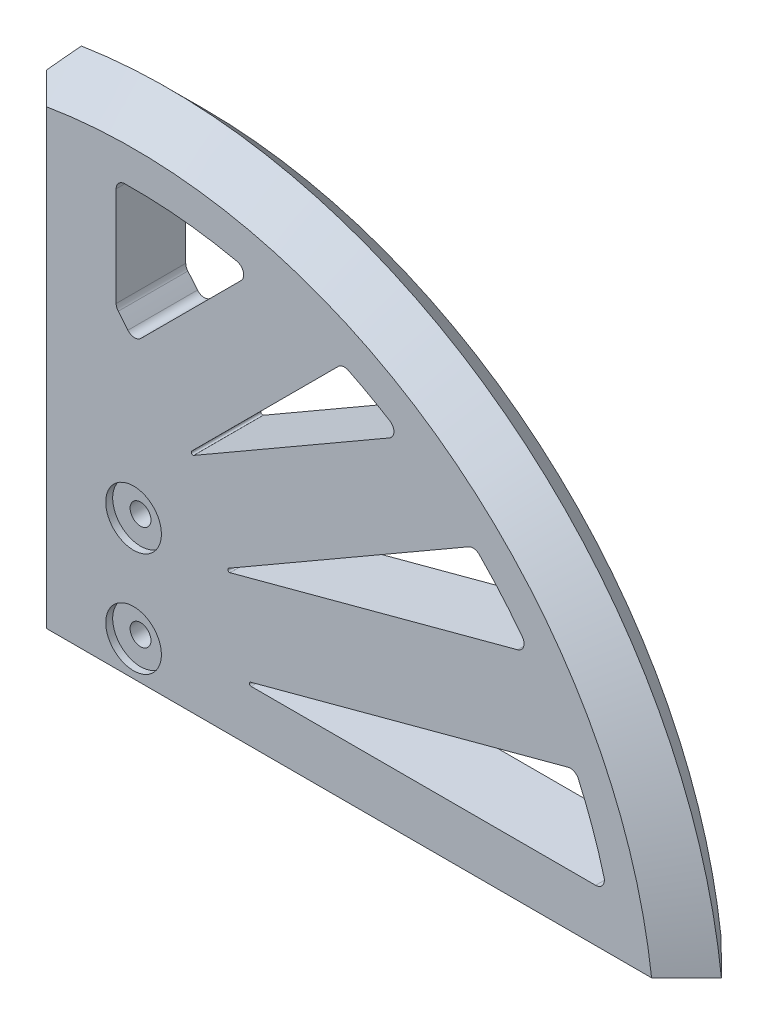
SolidWorks part; units mm, degrees
ref_plane "Front Plane" through (0, 0, 0) normal (0, 0, 1) x (1, 0, 0)
ref_plane "Top Plane" through (0, 0, 0) normal (0, 1, 0) x (1, 0, 0)
ref_plane "Right Plane" through (0, 0, 0) normal (1, 0, 0) x (0, 0, -1)
sketch "Sketch1" plane through (0, 0, 0) normal (0, 0, 1) x (1, 0, 0)
  line L0 (0, 0) -> (0, 27.8325)
  line L1 (0, 0) -> (37.7969, 0)
  line L3 (12, 3) -> (33.211, 3)
  line L6 (5, 18) -> (5, 24.3821)
  line L7 (12, 3) -> (31.3937, 8.1965)
  line L9 (10.8085, 7.8571) -> (28.7851, 12.6739)
  line L12 (10.8085, 7.8571) -> (25.5994, 16.3966)
  line L14 (8.8112, 12.4775) -> (21.4315, 19.7638)
  line L16 (8.8112, 12.4775) -> (18.0217, 21.6879)
  line L17 (12.8195, 23.5568) -> (6.0223, 16.7597)
  circle A2 centre (6, 2) radius 0.6
  circle A3 centre (6, 8) radius 0.6
  arc A17 (0, 27.8325) -> (37.7969, 0) centre (6, -3.6) cw
  arc A24 (5, 24.3821) -> (33.211, 3) centre (6, -3.6) cw
  arc A25 (5, 18) -> (12, 3) centre (-17.6305, -1.6942) cw
  point P36 (0, 0)
  dimension "D4" = 1.2
  dimension "D12" = 6
  dimension "D14" = 32
  dimension "D15" = 5
  dimension "D13" = 12
  dimension "D9" = 3
  dimension "D18" = 30
  dimension "D7" = 28
  dimension "D8" = 30
  dimension "D3" = 2
  dimension "D6" = 6
  dimension "D10" = 3.6
  dimension "D11" = 5
  dimension "D16" = 15
  dimension "D17" = 5
  dimension "D19" = 5
  dimension "D20" = 45
  dimension "20" = 18
  dimension "D5" = 2
extrude "Boss-Extrude1" add sketch "Sketch1" along normal blind 4 contours A17 L0 L1 A25 L6 A24 L3 A3 A2 | L9 A25 L7 A24 | L14 A25 L12 A24 | L6 A25 L16 A24 L17 region at (0.4728, 13.9162, 0) region at (20.8325, 7.9222, 0) region at (16.7737, 14.1119, 0) region at (11.5805, 18.6055, 0)
fillet "Fillet3" radius 0.1 3 edges at (8.8112, 12.4775, 2) (10.8085, 7.8571, 2) (12, 3, 2)
fillet "Fillet4" radius 0.5 10 edges at (33.211, 3, 2) (31.3937, 8.1965, 2) (28.7851, 12.6739, 2) (25.5994, 16.3966, 2) (21.4315, 19.7638, 2) (18.0217, 21.6879, 2) (12.8195, 23.5568, 2) (5, 24.3821, 2) (5, 18, 2) (6.0223, 16.7597, 2)
sketch "Sketch6" plane through (0, 0, 0) normal (0, -1, 0) x (1, 0, 0)
  line L0 (0, 2) -> (37.7969, 2) construction
  line L1 (0, 4) -> (0, 0) construction
  line L2 (37.7969, 4) -> (37.7969, 0) construction
  line L3 (6, 2.75) -> (6, 1.25) construction
  line L4 (8.75, 2.75) -> (3.25, 2.75)
  line L5 (8.75, 2.75) -> (8.75, 1.25)
  line L6 (8.75, 1.25) -> (3.25, 1.25)
  line L7 (3.25, 2.75) -> (3.25, 1.25)
  point P10 (8.75, 2)
  dimension "D1" = 1.5
  dimension "D2" = 6
  dimension "D3" = 5.5
extrude "Cut-Extrude3" cut sketch "Sketch6" against normal blind 12.5
chamfer "Chamfer5" distance 2 angle 45 1 edges at (24.9745, 22.1676, 0)
chamfer "Chamfer6" distance 2 angle 45 1 edges at (24.9745, 22.1676, 4)
chamfer "Chamfer7" distance 3 angle 45 1 edges at (0, 12.8969, 0)
chamfer "Chamfer8" distance 1 angle 45 1 edges at (0, 12.8969, 4)
sketch "Sketch8" plane through (0, 0, 4) normal (0, 0, 1) x (1, 0, 0)
  circle A2 centre (6, 8) radius 1.6
  circle A3 centre (6, 8) radius 1.6
  circle A5 centre (6, 2) radius 1.6
  circle A6 centre (6, 2) radius 1.6
  dimension "D1" = 1
  dimension "D2" = 1
extrude "Cut-Extrude4" cut sketch "Sketch8" against normal blind 0.4
extrude "Cut-Extrude5" cut sketch "Sketch8<2>" against normal blind 4 from offset 3.6 offset against normal yes
sketch "Sketch8<2>" plane through (0, 0, 4) normal (0, 0, 1) x (1, 0, 0) same geometry as "Sketch8"
